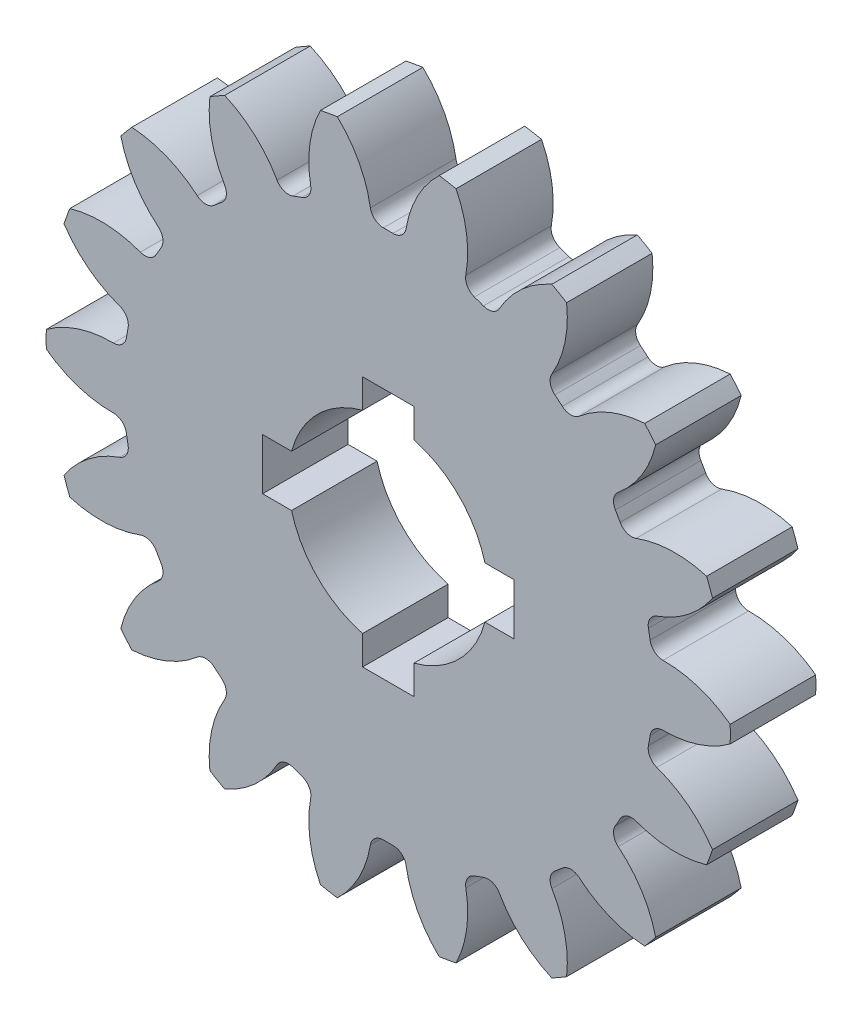
SolidWorks part; units mm, degrees
ref_plane "Front Plane" through (0, 0, 0) normal (0, 0, 1) x (1, 0, 0)
ref_plane "Top Plane" through (0, 0, 0) normal (0, 1, 0) x (1, 0, 0)
ref_plane "Right Plane" through (0, 0, 0) normal (1, 0, 0) x (0, 0, -1)
sketch "Sketch1" plane through (0, 0, 0) normal (0, 0, 1) x (1, 0, 0)
  line L4 (-0.969, 15.4697) -> (0, 0) construction
  line L5 (0, 0) -> (0, 20) construction
  line L6 (0, 0) -> (3.473, 19.6962) construction
  line L7 (-1.6208, 17.9269) -> (0.7404, 19.0363) construction
  line L8 (-1.6208, 17.9269) -> (0.3961, 18.1092) construction
  line L11 (1.6208, 17.9269) -> (-1.6208, 17.9269) construction
  circle A0 centre (0, 0) radius 15.5
  circle A1 centre (0, 0) radius 18 construction
  circle A2 centre (0, 0) radius 20
  arc A3 (-2.9795, 19.7768) -> (-0.969, 15.4697) centre (-7.4585, 15.0632) cw
  arc A4 (2.9795, 19.7768) -> (0.969, 15.4697) centre (7.4585, 15.0632) ccw
  point P5 (-18, 0)
  point P6 (-20, 0)
  point P7 (-15.5, 0)
  point P12 (-1.6208, 17.9269)
  point P22 (1.6208, 17.9269)
  dimension "D5" = 36
  dimension "D1" = 2.5
  dimension "D2" = 2
  dimension "D3" = 20
  dimension "D4" = 3.2416
  dimension "D6" = 10
  dimension "D7" = 0.5
extrude "Boss-Extrude1" add sketch "Sketch1" against normal blind 5 contours A2
extrude "Cut-Extrude1" cut sketch "Sketch1<4>" against normal blind 10 contours A4 A2 A3 A0 region at (0, 18.162, 0)
sketch "Sketch1<4>" plane through (0, 0, 0) normal (0, 0, 1) x (1, 0, 0) same geometry as "Sketch1"
fillet "Fillet2" radius 0.76 2 edges at (0.969, 15.4697, -2.5) (-0.969, 15.4697, -2.5)
ref_axis "Axis1" through (0, 0, 0) along (0, 0, 1)
pattern_circular "CirPattern2" count 18 over 360 about axis through (0, 0, 0) along (0, 0, 1) of "Cut-Extrude1", "Fillet2"
sketch "Sketch2" plane through (0, 0, 0) normal (0, 0, 1) x (1, 0, 0)
  line L0 (-1.5, 5.6528) -> (-1.5, 7.3485)
  line L1 (-1.5, 4.3485) -> (1.5, 4.3485) construction
  line L2 (-1.5, 4.3485) -> (-1.5, 7.3485) construction
  line L3 (-1.5, 7.3485) -> (1.5, 7.3485) construction
  line L4 (1.5, 4.3485) -> (1.5, 7.3485) construction
  line L5 (-1.5, 4.3485) -> (1.5, 7.3485) construction
  line L6 (-1.5, 7.3485) -> (1.5, 4.3485) construction
  line L7 (4.3485, -1.5) -> (7.3485, -1.5) construction
  line L8 (4.3485, -1.5) -> (4.3485, 1.5) construction
  line L9 (4.3485, 1.5) -> (7.3485, 1.5) construction
  line L10 (7.3485, -1.5) -> (7.3485, 1.5) construction
  line L11 (4.3485, -1.5) -> (7.3485, 1.5) construction
  line L12 (4.3485, 1.5) -> (7.3485, -1.5) construction
  line L13 (-1.5, -7.3485) -> (1.5, -7.3485) construction
  line L14 (-1.5, -7.3485) -> (-1.5, -4.3485) construction
  line L15 (-1.5, -4.3485) -> (1.5, -4.3485) construction
  line L16 (1.5, -7.3485) -> (1.5, -4.3485) construction
  line L17 (-1.5, -7.3485) -> (1.5, -4.3485) construction
  line L18 (-1.5, -4.3485) -> (1.5, -7.3485) construction
  line L19 (-7.3485, -1.5) -> (-4.3485, -1.5) construction
  line L20 (-7.3485, -1.5) -> (-7.3485, 1.5) construction
  line L21 (-7.3485, 1.5) -> (-4.3485, 1.5) construction
  line L22 (-4.3485, -1.5) -> (-4.3485, 1.5) construction
  line L23 (-7.3485, -1.5) -> (-4.3485, 1.5) construction
  line L24 (-7.3485, 1.5) -> (-4.3485, -1.5) construction
  line L25 (-1.5, 7.3485) -> (1.5, 7.3485)
  line L26 (1.5, 7.3485) -> (1.5, 5.6528)
  line L27 (5.6528, 1.5) -> (7.3485, 1.5)
  line L28 (7.3485, 1.5) -> (7.3485, -1.5)
  line L29 (7.3485, -1.5) -> (5.6528, -1.5)
  line L30 (1.5, -7.3485) -> (1.5, -5.6528)
  line L31 (1.5, -7.3485) -> (-1.5, -7.3485)
  line L32 (-1.5, -7.3485) -> (-1.5, -5.6528)
  line L33 (-5.6528, -1.5) -> (-7.3485, -1.5)
  line L34 (-7.3485, -1.5) -> (-7.3485, 1.5)
  line L35 (-7.3485, 1.5) -> (-5.6528, 1.5)
  circle A0 centre (0, 0) radius 7.5 construction
  arc A1 (-1.5, 5.6528) -> (-5.6528, 1.5) centre (0, 0) ccw
  arc A2 (5.6528, 1.5) -> (1.5, 5.6528) centre (0, 0) ccw
  arc A3 (1.5, -5.6528) -> (5.6528, -1.5) centre (0, 0) ccw
  arc A4 (-5.6528, -1.5) -> (-1.5, -5.6528) centre (0, 0) ccw
  point P3 (0, 5.8485)
  point P8 (5.8485, 0)
  point P13 (0, -5.8485)
  point P18 (-5.8485, 0)
  dimension "D1" = 15
  dimension "D2" = 3
extrude "Cut-Extrude2" cut sketch "Sketch2" against normal up to surface (5 mm away) up to face at (0, 0, -5)
equation "\"backlash\"= 0.1mm"
equation "\"module\"= 2mm"
equation "\"pressureAngle\"= 20deg"
equation "\"width\"= 10mm"
equation "\"D1@Sketch1\"= 1.25 * \"module\""
equation "\"D2@Sketch1\"=\"module\""
equation "\"D5@Sketch1\"=\"module\"*\"numberOfTeeth\""
equation "\"D1@Boss-Extrude1\"=\"width\"-5"
equation "\"D3@Sketch1\"=\"pressureAngle\""
equation "\"D1@Cut-Extrude1\"=\"width\""
equation "\"D1@CirPattern2\"=\"numberOfTeeth\""
equation "\"D1@Fillet2\"=0.38*\"module\""
equation "\"D4@Sketch1\"=pi*\"module\"/2+\"backlash\""
equation "\"numberOfTeeth\"= 18"
equation "\"D6@Sketch1\"=180/\"numberOfTeeth\""
equation "\"toothTipProfile\"= 1mm"
equation "\"D7@Sketch1\"=\"toothTipProfile\"/2"
equation "\"lengthOverallRack\"= pi * \"module\" * \"numberOfTeethRack\""
equation "\"numberOfTeethRack\"= 20"
